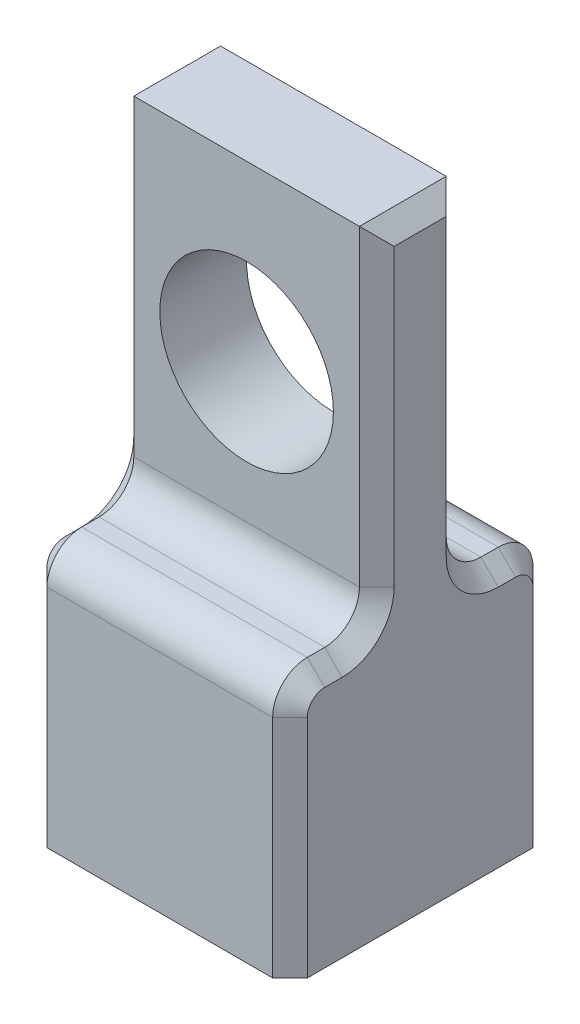
SolidWorks part; units mm, degrees
ref_plane "Front Plane" through (0, 0, 0) normal (0, 0, 1) x (1, 0, 0)
ref_plane "Top Plane" through (0, 0, 0) normal (0, 1, 0) x (1, 0, 0)
ref_plane "Right Plane" through (0, 0, 0) normal (1, 0, 0) x (0, 0, -1)
sketch "Sketch1" plane through (0, 0, 0) normal (0, 1, 0) x (1, 0, 0)
  line L1 (7.5, 7.5) -> (-7.5, 7.5)
  line L2 (7.5, 7.5) -> (7.5, -7.5)
  line L3 (7.5, -7.5) -> (-7.5, -7.5)
  line L4 (-7.5, 7.5) -> (-7.5, -7.5)
  line L5 (7.5, 7.5) -> (-7.5, -7.5) construction
  line L6 (7.5, -7.5) -> (-7.5, 7.5) construction
  point P0 (0, 0)
  dimension "D1" = 15
  dimension "D2" = 15
extrude "Boss-Extrude1" add sketch "Sketch1" along normal blind 35
sketch "Sketch2" plane through (0, 0, 7.5) normal (0, 0, 1) x (1, 0, 0)
  line L0 (-7.5, 0) -> (7.5, 0) construction
  circle A0 centre (0, 25) radius 5
  dimension "D1" = 10
  dimension "D2" = 25
extrude "Cut-Extrude1" cut sketch "Sketch2" against normal blind 25
sketch "Sketch3" plane through (0, 35, 0) normal (0, 1, 0) x (1, 0, 0)
  line L0 (7.5, -7.5) -> (7.5, 7.5) construction
  line L1 (-7.5, 7.5) -> (7.5, 7.5)
  line L2 (-7.5, 7.5) -> (-7.5, 2.5)
  line L3 (-7.5, 2.5) -> (7.5, 2.5)
  line L4 (7.5, 7.5) -> (7.5, 2.5)
  line L5 (-7.5, 7.5) -> (-7.5, -7.5) construction
  line L6 (7.5, -7.5) -> (-7.5, -7.5)
  line L7 (7.5, -7.5) -> (7.5, -2.5)
  line L8 (7.5, -2.5) -> (-7.5, -2.5)
  line L9 (-7.5, -7.5) -> (-7.5, -2.5)
  dimension "D1" = 5
  dimension "D2" = 5
  dimension "D3" = 5
extrude "Cut-Extrude2" cut sketch "Sketch3" against normal blind 20
fillet "Fillet4" radius 2 4 edges at (0, 15, 7.5) (0, 15, -7.5) (0, 15, -2.5) (0, 15, 2.5)
chamfer "Chamfer1" distance 1 angle 45 22 edges at (7.5, 35, 0) (-7.5, 35, 0) (-7.5, 6.5, 7.5) (-7.5, 14.4142, 6.9142) (-7.5, 15, 5) (-7.5, 26, 2.5) (-7.5, 15.5858, 3.0858) (-7.5, 26, -2.5) (-7.5, 15.5858, -3.0858) (-7.5, 15, -5) (-7.5, 6.5, -7.5) (-7.5, 14.4142, -6.9142) (7.5, 6.5, -7.5) (7.5, 14.4142, -6.9142) (7.5, 15, -5) (7.5, 26, -2.5) (7.5, 15.5858, -3.0858) (7.5, 26, 2.5) (7.5, 15.5858, 3.0858) (7.5, 15, 5) (7.5, 6.5, 7.5) (7.5, 14.4142, 6.9142)
sketch "Sketch4" plane through (0, 0, 0) normal (0, -1, 0) x (1, 0, 0)
  line L0 (-6.5, 7.5) -> (6.5, 7.5) construction
  circle A0 centre (0, 4) radius 1.5
  circle A1 centre (0, -4) radius 1.5
  dimension "D1" = 3
  dimension "D2" = 3
  dimension "D3" = 8
  dimension "D4" = 3.5
extrude "Cut-Extrude3" cut sketch "Sketch4" against normal blind 10
